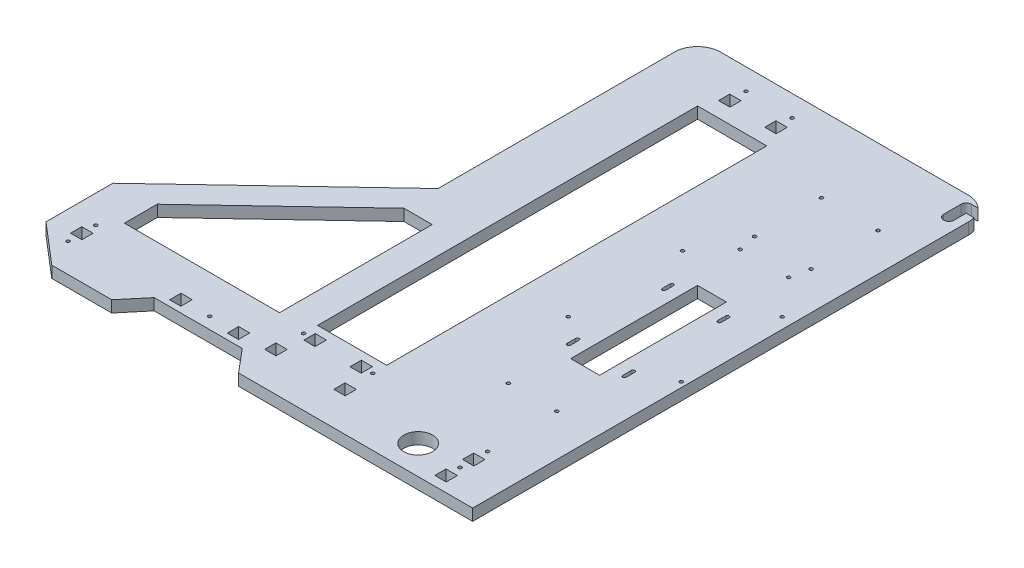
SolidWorks part; units mm, degrees
ref_plane "Front Plane" through (0, 0, 0) normal (0, 0, 1) x (1, 0, 0)
ref_plane "Top Plane" through (0, 0, 0) normal (0, 1, 0) x (1, 0, 0)
ref_plane "Right Plane" through (0, 0, 0) normal (1, 0, 0) x (0, 0, -1)
sketch "Sketch1" plane through (0, 0, 0) normal (0, 1, 0) x (1, 0, 0)
  line L0 (0, 0) -> (-235, 0)
  line L1 (-235, 0) -> (-235, -225)
  line L2 (-235, -225) -> (-380, -362)
  line L3 (-380, -362) -> (-380, -420)
  line L4 (-380, -420) -> (-345, -450)
  line L5 (-345, -450) -> (-293, -450)
  line L6 (-293, -450) -> (-263.6315, -415)
  line L7 (-263.6315, -415) -> (-212.3685, -415)
  line L8 (-212.3685, -415) -> (-183, -450)
  line L9 (-183, -450) -> (0, -450)
  line L10 (0, 0) -> (0, -450)
  line L12 (-293, -450) -> (-183, -450) construction
  dimension "D3" = 235
  dimension "D5" = 58
  dimension "D13" = 190
  dimension "D7" = 35
  dimension "D15" = 52
  dimension "D12" = 30
  dimension "D10" = 35
  dimension "D6" = 380
  dimension "D4" = 450
  dimension "D2" = 50
  dimension "D8" = 50
  dimension "D9" = 110
extrude "Boss-Extrude1" add sketch "Sketch1" along normal blind 10
sketch "Sketch16" plane through (0, 10, 0) normal (0, 1, 0) x (1, 0, 0)
  line L0 (0, -450) -> (20, -450)
  line L1 (20, -450) -> (20, 0)
  line L2 (20, 0) -> (0, 0)
  line L3 (0, 0) -> (0, -450)
  dimension "D1" = 20
  dimension "D2" = 90
extrude "Boss-Extrude2" add sketch "Sketch16" against normal through all
sketch "Sketch2" plane through (0, 10, 0) normal (0, 1, 0) x (1, 0, 0)
  line L0 (-235, -225) -> (-235, -415) construction
  line L1 (-263.6315, -415) -> (-212.3685, -415) construction
  line L2 (-345, -450) -> (-345, -328.931) construction
  line L3 (-235, -225) -> (-380, -362) construction
  line L4 (-345, -358.5097) -> (-235, -254.5787)
  line L5 (-235, -254.5787) -> (-210.5, -254.5787)
  line L6 (-210.5, -254.5787) -> (-210.5, -387)
  line L7 (-210.5, -387) -> (-345, -387)
  line L8 (-345, -387) -> (-345, -358.5097)
  line L9 (0, -450) -> (0, 0) construction
  line L10 (-184.5, -380) -> (-124.5, -380)
  line L11 (-184.5, -380) -> (-184.5, -50.425)
  line L12 (-184.5, -50.425) -> (-124.5, -50.425)
  line L13 (-124.5, -380) -> (-124.5, -50.425)
  line L14 (-124.5, -392.1) -> (-184.5, -392.1) construction
  line L15 (-16, -450) -> (-16, 0) construction
  line L16 (20, 0) -> (-235, 0) construction
  line L17 (-355.9, -440.6571) -> (-355.9, -339.2297) construction
  line L18 (-20.925, -441.85) -> (-11.075, -441.85)
  line L19 (-20.925, -441.85) -> (-20.925, -432.15)
  line L20 (-20.925, -432.15) -> (-11.075, -432.15)
  line L21 (-11.075, -441.85) -> (-11.075, -432.15)
  line L22 (-20.925, -441.85) -> (-11.075, -432.15) construction
  line L23 (-20.925, -432.15) -> (-11.075, -441.85) construction
  line L24 (-20.925, -417.85) -> (-11.075, -417.85)
  line L25 (-20.925, -417.85) -> (-20.925, -408.15)
  line L26 (-20.925, -408.15) -> (-11.075, -408.15)
  line L27 (-11.075, -417.85) -> (-11.075, -408.15)
  line L28 (-20.925, -417.85) -> (-11.075, -408.15) construction
  line L29 (-20.925, -408.15) -> (-11.075, -417.85) construction
  line L30 (-380, -420) -> (-345, -450) construction
  line L32 (-350.975, -408.15) -> (-360.825, -408.15)
  line L33 (-350.975, -408.15) -> (-350.975, -417.85)
  line L34 (-350.975, -417.85) -> (-360.825, -417.85)
  line L35 (-360.825, -408.15) -> (-360.825, -417.85)
  line L36 (-350.975, -408.15) -> (-360.825, -417.85) construction
  line L37 (-350.975, -417.85) -> (-360.825, -408.15) construction
  line L38 (-183, -450) -> (20, -450) construction
  line L39 (-183, -450) -> (20, -450) construction
  line L40 (-173.749, -32.425) -> (-113.749, -32.425) construction
  line L41 (-154.5, -50.425) -> (-154.5, -32.425) construction
  line L42 (-179.425, -27.575) -> (-169.575, -27.575)
  line L43 (-179.425, -27.575) -> (-179.425, -37.275)
  line L44 (-179.425, -37.275) -> (-169.575, -37.275)
  line L45 (-169.575, -27.575) -> (-169.575, -37.275)
  line L46 (-179.425, -27.575) -> (-169.575, -37.275) construction
  line L47 (-179.425, -37.275) -> (-169.575, -27.575) construction
  line L48 (-129.575, -37.275) -> (-139.425, -27.575) construction
  line L49 (-129.575, -27.575) -> (-139.425, -37.275) construction
  line L50 (-139.425, -27.575) -> (-139.425, -37.275)
  line L51 (-129.575, -37.275) -> (-139.425, -37.275)
  line L52 (-129.575, -27.575) -> (-129.575, -37.275)
  line L53 (-129.575, -27.575) -> (-139.425, -27.575)
  line L54 (-174.5, -32.425) -> (-174.5, -18.425) construction
  line L55 (-134.5, -32.425) -> (-134.5, -18.425) construction
  line L56 (-154.5, -380) -> (-154.5, -450) construction
  line L57 (-174.5, -392.1) -> (-134.5, -392.1) construction
  line L58 (-129.65, -397.025) -> (-139.35, -387.175) construction
  line L59 (-179.35, -387.175) -> (-169.65, -387.175)
  line L60 (-179.35, -387.175) -> (-179.35, -397.025)
  line L61 (-179.35, -397.025) -> (-169.65, -397.025)
  line L62 (-169.65, -387.175) -> (-169.65, -397.025)
  line L63 (-179.35, -387.175) -> (-169.65, -397.025) construction
  line L64 (-179.35, -397.025) -> (-169.65, -387.175) construction
  line L65 (-129.65, -387.175) -> (-139.35, -397.025) construction
  line L66 (-139.35, -387.175) -> (-139.35, -397.025)
  line L67 (-129.65, -397.025) -> (-139.35, -397.025)
  line L68 (-129.65, -387.175) -> (-129.65, -397.025)
  line L69 (-129.65, -387.175) -> (-139.35, -387.175)
  line L70 (-119.575, -420.95) -> (-129.425, -411.25) construction
  line L71 (-189.425, -411.25) -> (-179.575, -411.25)
  line L72 (-189.425, -411.25) -> (-189.425, -420.95)
  line L73 (-189.425, -420.95) -> (-179.575, -420.95)
  line L74 (-179.575, -411.25) -> (-179.575, -420.95)
  line L75 (-189.425, -411.25) -> (-179.575, -420.95) construction
  line L76 (-189.425, -420.95) -> (-179.575, -411.25) construction
  line L77 (-119.575, -411.25) -> (-129.425, -420.95) construction
  line L78 (-129.425, -411.25) -> (-129.425, -420.95)
  line L79 (-119.575, -420.95) -> (-129.425, -420.95)
  line L80 (-119.575, -411.25) -> (-119.575, -420.95)
  line L81 (-119.575, -411.25) -> (-129.425, -411.25)
  line L82 (-360.825, -408.15) -> (-11.075, -408.15) construction
  circle A0 centre (-16, -425) radius 1.45
  circle A1 centre (-16, -401) radius 1.45
  circle A2 centre (-355.9, -425) radius 1.45
  circle A3 centre (-355.9, -401) radius 1.45
  circle A4 centre (-174.5, -18.425) radius 1.45
  circle A5 centre (-134.5, -18.425) radius 1.45
  circle A6 centre (-124.5, -392.1) radius 1.45
  circle A7 centre (-184.5, -392.1) radius 1.45
  point P25 (-16, -437)
  point P30 (-16, -413)
  point P44 (-355.9, -413)
  point P61 (-174.5, -32.425)
  point P72 (-134.5, -32.425)
  point P85 (-174.5, -392.1)
  point P94 (-134.5, -392.1)
  point P95 (-184.5, -416.1)
  point P104 (-124.5, -416.1)
  point P105 (-154.5, -392.1)
  dimension "D13" = 2.9
  dimension "D14" = 2.9
  dimension "D23" = 2.9
  dimension "D24" = 2.9
  dimension "D31" = 2.9
  dimension "D37" = 2.9
  dimension "D1" = 21.5
  dimension "D2" = 28
  dimension "D3" = 24.5
  dimension "D4" = 60
  dimension "D7" = 26
  dimension "D8" = 9.7
  dimension "D9" = 9.85
  dimension "D10" = 9.85
  dimension "D11" = 9.7
  dimension "D12" = 24
  dimension "D15" = 24
  dimension "D19" = 9.85
  dimension "D20" = 9.7
  dimension "D26" = 12
  dimension "D27" = 9.85
  dimension "D28" = 9.7
  dimension "D33" = 9.7
  dimension "D38" = 9.85
  dimension "D39" = 9.7
  dimension "D41" = 24
  dimension "D34" = 30
  dimension "D36" = 12.1
  dimension "D30" = 18
  dimension "D29" = 40
  dimension "D17" = 13
  dimension "D32" = 14
  dimension "D35" = 20
  dimension "D16" = 12
  dimension "D21" = 90
  dimension "D25" = 24
  dimension "D5" = 359.75
  dimension "D22" = 349.75
  dimension "D40" = 30
  dimension "D6" = 70
  dimension "D42" = 0
  dimension "D43" = 0
  dimension "D18" = 16
  dimension "D44" = 9.85
extrude "Cut-Extrude1" cut sketch "Sketch2" against normal through all
fillet "Fillet1" radius 20 2 edges at (-235, 5, 0) (20, 5, 0)
sketch "Sketch11" plane through (0, 10, 0) normal (0, 1, 0) x (1, 0, 0)
  line L0 (-124.5, -215.2125) -> (20, -215.2125) construction
  line L1 (20, -450) -> (20, -20) construction
  line L3 (-52.25, -215.2125) -> (-52.25, -450) construction
  line L6 (-124.5, -380) -> (-124.5, -50.425) construction
  line L8 (-183, -450) -> (20, -450) construction
  circle A0 centre (-52.25, -425) radius 12.5
  circle A1 centre (-16, -425) radius 1.45 construction
  dimension "D1" = 25
  dimension "D2" = 0
  dimension "D3" = 0
extrude "WiringHole" cut sketch "Sketch11" against normal through all
sketch "Sketch9" [suppressed] plane through (0, 10, 0) normal (0, 1, 0) x (1, 0, 0)
  line L0 (-52.25, -412.5) -> (-52.25, 0) construction
  line L1 (0, 0) -> (-215, 0) construction
  line L2 (-124.5, -215.2125) -> (20, -215.2125) construction
  line L3 (-124.5, -380) -> (-124.5, -50.425) construction
  line L4 (-4.75, -126.7125) -> (-4.75, -303.7125) construction
  line L6 (-99.75, -126.7125) -> (-4.75, -126.7125) construction
  line L7 (-4.75, -303.7125) -> (-99.75, -303.7125) construction
  line L8 (-99.75, -303.7125) -> (-99.75, -126.7125) construction
  line L9 (20, -450) -> (20, -20) construction
  circle A0 centre (-52.25, -425) radius 12.5 construction
  circle A1 centre (-99.75, -126.7125) radius 1.45
  circle A2 centre (-4.75, -126.7125) radius 1.45
  circle A3 centre (-4.75, -303.7125) radius 1.45
  circle A4 centre (-99.75, -303.7125) radius 1.45
  dimension "D3" = 2.9
  dimension "D4" = 2.9
  dimension "D1" = 95
  dimension "D2" = 177
  dimension "D5" = 47.5
extrude "MountingHoles-PSU" [suppressed] cut sketch "Sketch9" against normal through all
sketch "Sketch10" plane through (0, 10, 0) normal (0, 1, 0) x (1, 0, 0)
  line L0 (-124.5, -215.2125) -> (20, -215.2125) construction
  line L1 (20, -450) -> (20, -20) construction
  line L2 (-49.75, -240.2125) -> (-24.75, -240.2125) construction
  line L3 (-37.25, -210.225) -> (-37.25, 0) construction
  line L4 (-52.25, -215.2125) -> (-52.25, -184.5972) construction
  line L7 (-124.5, -380) -> (-124.5, -50.425) construction
  line L8 (-49.75, -295.2125) -> (-24.75, -295.2125)
  line L9 (-49.75, -295.2125) -> (-49.75, -185.2125)
  line L10 (-49.75, -185.2125) -> (-24.75, -185.2125)
  line L11 (-24.75, -295.2125) -> (-24.75, -185.2125)
  line L12 (-49.75, -295.2125) -> (-24.75, -185.2125) construction
  line L13 (-49.75, -185.2125) -> (-24.75, -295.2125) construction
  line L15 (0, 0) -> (-215, 0) construction
  line L17 (-37.25, -210.225) -> (-37.25, -450) construction
  line L18 (-183, -450) -> (20, -450) construction
  line L19 (-64.75, -215.2125) -> (-39.75, -215.2125) construction
  line L20 (-37.25, -295.2125) -> (-37.25, -185.2125) construction
  dimension "D1" = 25
  dimension "D2" = 110
  dimension "D3" = 0
  dimension "D4" = 0
  dimension "D5" = 0
  dimension "D6" = 25
  dimension "D7" = 15
extrude "WiringSlot" cut sketch "Sketch10" against normal through all
sketch "CenterLines" plane through (0, 10, 0) normal (0, 1, 0) x (1, 0, 0)
  line L0 (-37.25, -295.2125) -> (-37.25, -185.2125) construction
  line L1 (-49.75, -295.2125) -> (-24.75, -295.2125) construction
  line L2 (-24.75, -185.2125) -> (-49.75, -185.2125) construction
  line L3 (-49.75, -240.2125) -> (-24.75, -240.2125) construction
  line L4 (-49.75, -185.2125) -> (-49.75, -295.2125) construction
  line L5 (-24.75, -295.2125) -> (-24.75, -185.2125) construction
ref_plane "Plane1" through (-37.25, 0, 0) normal (1, 0, 0) x (0, 0, -1)
sketch "Sketch6" plane through (0, 10, 0) normal (0, 1, 0) x (1, 0, 0)
  line L0 (-37.25, -295.2125) -> (-37.25, -185.2125) construction
  line L1 (-61.35, -240.2125) -> (-13.15, -240.2125) construction
  line L2 (-13.15, -195.7625) -> (-13.15, -278.2625) construction
  line L3 (-49.75, -295.2125) -> (-24.75, -295.2125) construction
  line L4 (-49.75, -240.2125) -> (-24.75, -240.2125) construction
  line L5 (-24.75, -185.2125) -> (-49.75, -185.2125) construction
  line L6 (-13.15, -195.7625) -> (-13.15, -202.7625) construction
  line L7 (-11.7, -195.7625) -> (-11.7, -202.7625)
  line L8 (-14.6, -195.7625) -> (-14.6, -202.7625)
  line L9 (-49.75, -240.2125) -> (-24.75, -240.2125) construction
  line L10 (-49.75, -185.2125) -> (-49.75, -295.2125) construction
  line L11 (-24.75, -295.2125) -> (-24.75, -185.2125) construction
  line L12 (-13.15, -285.2625) -> (-13.15, -278.2625) construction
  line L13 (-14.6, -285.2625) -> (-14.6, -278.2625)
  line L14 (-61.35, -277.6625) -> (-61.35, -202.7625) construction
  line L15 (-13.15, -285.2625) -> (-13.15, -202.7625) construction
  line L16 (-11.7, -285.2625) -> (-11.7, -278.2625)
  arc A2 (-11.7, -195.7625) -> (-14.6, -195.7625) centre (-13.15, -195.7625) ccw
  arc A3 (-14.6, -202.7625) -> (-11.7, -202.7625) centre (-13.15, -202.7625) ccw
  circle A4 centre (-61.35, -277.6625) radius 1.45
  circle A6 centre (-61.35, -202.7625) radius 1.45
  arc A8 (-14.6, -285.2625) -> (-11.7, -285.2625) centre (-13.15, -285.2625) ccw
  arc A9 (-11.7, -278.2625) -> (-14.6, -278.2625) centre (-13.15, -278.2625) ccw
  point P20 (-13.15, -199.2625)
  point P25 (-13.15, -281.7625)
  dimension "D6" = 0
  dimension "D8" = 2.9
  dimension "D12" = 2.9
  dimension "D4" = 1.45
  dimension "D5" = 1.45
  dimension "D11" = 82.5
  dimension "D14" = 74.9
  dimension "D2" = 24.1
  dimension "D3" = 48.2
  dimension "D9" = 7
  dimension "D10" = 7
extrude "MountingHoles-RAMPS" cut sketch "Sketch6" against normal through all
mirror "Mirror1" about plane through (-37.25, 0, 0) normal (1, 0, 0) of "MountingHoles-RAMPS"
sketch "Sketch5" plane through (0, 10, 0) normal (0, 1, 0) x (1, 0, 0)
  line L0 (-24.75, -240.2125) -> (-49.75, -240.2125) construction
  line L3 (-24.75, -295.2125) -> (-24.75, -185.2125) construction
  line L5 (-49.75, -185.2125) -> (-49.75, -295.2125) construction
  line L7 (-16.25, -139.7125) -> (-58.25, -139.7125) construction
  line L8 (-16.25, -340.7125) -> (-58.25, -340.7125) construction
  line L9 (-37.25, -240.2125) -> (-37.25, -139.7125) construction
  line L10 (-37.25, -240.2125) -> (-37.25, -340.7125) construction
  circle A0 centre (-58.25, -139.7125) radius 1.45
  circle A1 centre (-16.25, -139.7125) radius 1.45
  circle A2 centre (-16.25, -340.7125) radius 1.45
  circle A3 centre (-58.25, -340.7125) radius 1.45
  point P17 (-37.25, -139.7125)
  point P22 (-37.25, -340.7125)
  dimension "D2" = 2.9
  dimension "D5" = 2.9
  dimension "D6" = 2.9
  dimension "D7" = 2.9
  dimension "D3" = 201
  dimension "D4" = 100.5
  dimension "D8" = 21
  dimension "D9" = 21
  dimension "D10" = 100.5
extrude "MountingHoles-Melzi" cut sketch "Sketch5" against normal through all
sketch "Sketch13" plane through (0, 0, 0) normal (0, -1, 0) x (-1, 0, 0)
  line L0 (49.75, -215.2125) -> (124.5, -215.2125) construction
  line L1 (124.5, -380) -> (124.5, -50.425) construction
  line L2 (82.25, -264.7275) -> (82.25, -165.6975) construction
  line L3 (37.25, -295.2125) -> (37.25, -185.2125) construction
  line L4 (49.75, -185.2125) -> (49.75, -295.2125) construction
  line L6 (82.25, -264.7275) -> (-15.65, -264.7275) construction
  circle A0 centre (82.25, -165.6975) radius 1.45
  circle A1 centre (82.25, -264.7275) radius 1.45
  circle A2 centre (-10.59, -172.1775) radius 1.45
  circle A3 centre (-15.65, -264.7275) radius 1.45
  point P11 (82.25, -215.2125)
  dimension "D8" = 2.9
  dimension "D6" = 2.9
  dimension "D1" = 2.9
  dimension "D2" = 49.515
  dimension "D3" = 45
  dimension "D4" = 6.48
  dimension "D5" = 92.84
  dimension "D7" = 97.9
extrude "Mountingholes-Smoothieboard" cut sketch "Sketch13" against normal through all
mirror "Flipped" [suppressed] about plane through (-37.25, 0, 0) normal (1, 0, 0)
sketch "Sketch21" plane through (0, 10, 0) normal (0, 1, 0) x (1, 0, 0)
  line L0 (-37.25, -185.2125) -> (-37.25, 0) construction
  line L1 (-24.75, -185.2125) -> (-49.75, -185.2125) construction
  line L2 (0, 0) -> (-215, 0) construction
  line L3 (-37.25, -94.7125) -> (-23.3697, -94.7125) construction
  circle A0 centre (-12.75, -65.7125) radius 1.45
  circle A1 centre (-61.75, -65.7125) radius 1.45
  circle A2 centre (-61.75, -123.7125) radius 1.45
  circle A3 centre (-12.75, -123.7125) radius 1.45
  circle A4 centre (-16.25, -139.7125) radius 1.45 construction
  dimension "D1" = 2.9
  dimension "D2" = 24.5
  dimension "D3" = 29
  dimension "D4" = 45
extrude "Pi" cut sketch "Sketch21" against normal through all
sketch "Sketch17" plane through (0, 10, 0) normal (0, 1, 0) x (1, 0, 0)
  line L0 (0, 0) -> (20, 0) construction
  line L1 (20, -23.6361) -> (20, 0) construction
  line L2 (20, -450) -> (20, -20) construction
  line L3 (20, -10) -> (8, -10) construction
  line L4 (20, -14.5) -> (8, -14.5)
  line L5 (20, -5.5) -> (8, -5.5)
  arc A0 (20, -14.5) -> (20, -5.5) centre (20, -10) ccw
  arc A1 (8, -5.5) -> (8, -14.5) centre (8, -10) ccw
  point P8 (14, -10)
  dimension "D1" = 9
  dimension "D2" = 12
  dimension "D3" = 10
extrude "Cut-Extrude3" cut sketch "Sketch17" against normal through all
sketch "Sketch18" plane through (0, 10, 0) normal (0, 1, 0) x (1, 0, 0)
  line L0 (8, -5.5) -> (8, -14.5) construction
  line L1 (3.5, -10) -> (8, -10) construction
  line L2 (8, -10) -> (8, -25) construction
  line L3 (12.5, -10) -> (12.5, -25)
  line L4 (3.5, -10) -> (3.5, -25)
  arc A0 (8, -5.5) -> (8, -14.5) centre (8, -10) ccw construction
  arc A1 (12.5, -10) -> (3.5, -10) centre (8, -10) ccw
  arc A2 (3.5, -25) -> (12.5, -25) centre (8, -25) ccw
  point P10 (8, -17.5)
  dimension "D1" = 9
  dimension "D2" = 0
  dimension "D3" = 15
extrude "Cut-Extrude4" cut sketch "Sketch18" against normal through all
sketch "Sketch19" plane through (0, 10, 0) normal (0, 1, 0) x (1, 0, 0)
  line L0 (-2, -25) -> (18, -25) construction
  line L1 (8, -25) -> (8, -5.5) construction
  circle A0 centre (18, -25) radius 1.45
  arc A1 (8, -5.5) -> (3.5, -10) centre (8, -10) ccw construction
  circle A2 centre (-2, -25) radius 1.45
  dimension "D2" = 2.9
extrude "Cut-Extrude5" [suppressed] cut sketch "Sketch19" against normal through all
sketch "Sketch22" plane through (0, 10, 0) normal (0, 1, 0) x (1, 0, 0)
  line L0 (-276.218, -430) -> (-199.782, -430)
  line L1 (-293, -450) -> (-263.6315, -415) construction
  line L2 (-212.3685, -415) -> (-183, -450) construction
  line L3 (-199.782, -430) -> (-212.3685, -415)
  line L4 (-212.3685, -415) -> (-263.6315, -415)
  line L5 (-263.6315, -415) -> (-276.218, -430)
  dimension "D1" = 15
extrude "Boss-Extrude3" add sketch "Sketch22" against normal through all
sketch "Sketch23" plane through (0, 10, 0) normal (0, 1, 0) x (1, 0, 0)
  line L0 (-238, -430) -> (-238, -387) construction
  line L1 (-276.218, -430) -> (-199.782, -430) construction
  line L2 (-345, -387) -> (-210.5, -387) construction
  line L3 (-213, -420) -> (-263, -420) construction
  line L4 (-179.35, -387.175) -> (-179.35, -397.025) construction
  line L5 (-267.85, -415.075) -> (-258.15, -415.075)
  line L6 (-267.85, -415.075) -> (-267.85, -424.925)
  line L7 (-267.85, -424.925) -> (-258.15, -424.925)
  line L8 (-258.15, -415.075) -> (-258.15, -424.925)
  line L9 (-267.85, -415.075) -> (-258.15, -424.925) construction
  line L10 (-267.85, -424.925) -> (-258.15, -415.075) construction
  line L11 (-208.15, -424.925) -> (-217.85, -415.075) construction
  line L12 (-208.15, -415.075) -> (-217.85, -424.925) construction
  line L13 (-217.85, -415.075) -> (-217.85, -424.925)
  line L14 (-208.15, -424.925) -> (-217.85, -424.925)
  line L15 (-208.15, -415.075) -> (-208.15, -424.925)
  line L16 (-208.15, -415.075) -> (-217.85, -415.075)
  circle A0 centre (-238, -420) radius 1.45
  point P19 (-238, -420)
  dimension "D4" = 2.9
  dimension "D1" = 9.7
  dimension "D3" = 10
extrude "Cut-Extrude6" cut sketch "Sketch23" against normal through all
equation "\"Y-ROD-SPACING\"=75"
equation "\"Y-BED-OFFSET\"=2"
equation "\"Y-BED-ROD-INSET\"=3.5"
equation "\"T-SLOT-NUT-FILLET-RADIUS\"=0.5"
equation "\"T-SLOT-SCREW-SHAFT-RADIUS\"=1.55"
equation "\"T-SLOT-SCREW-SHAFT-CUTOUT-LENGTH\"=11"
equation "\"T-SLOT-NUT-DEPTH\"=3.5"
equation "\"T-SLOT-NUT-WIDTH\"=2.85"
equation "\"T-SLOT-NUT-END-DISTANCE\"=8"
equation "\"ACRYLIC-TAB-CUTOUT-SIZE\"=\"ACRYLIC-THICKNESS\"+\"ACRYLIC-TAB-TOLERANCE\"*2"
equation "\"ACRYLIC-TAB-WIDTH\"=\"ACRYLIC-THICKNESS\""
equation "\"ACRYLIC-M3-HOLE\"=2.9"
equation "\"SMOOTHROD-CAP-SCREW-DISTANCE\"=20"
equation "\"FRAME-WIDTH-INNER\"=370"
equation "\"D24@Sketch2\"=\"ACRYLIC-M3-HOLE\""
equation "\"D23@Sketch2\"=\"ACRYLIC-M3-HOLE\""
equation "\"D19@Sketch2\"=\"ACRYLIC-THICKNESS\"-\"KERF\"*2"
equation "\"D20@Sketch2\"=\"ACRYLIC-TAB-WIDTH\"-\"KERF\"*4"
equation "\"D37@Sketch2\"=\"ACRYLIC-M3-HOLE\""
equation "\"D33@Sketch2\"=\"ACRYLIC-TAB-WIDTH\"-\"KERF\"*4"
equation "\"D38@Sketch2\"=\"ACRYLIC-THICKNESS\"-\"KERF\"*2"
equation "\"D39@Sketch2\"=\"ACRYLIC-TAB-WIDTH\"-\"KERF\"*4"
equation "\"D13@Sketch2\"=\"ACRYLIC-M3-HOLE\""
equation "\"D14@Sketch2\"=\"ACRYLIC-M3-HOLE\""
equation "\"D8@Sketch2\"=\"ACRYLIC-TAB-WIDTH\"-\"KERF\"*4"
equation "\"D9@Sketch2\"=\"ACRYLIC-THICKNESS\"-\"KERF\"*2"
equation "\"D10@Sketch2\"=\"ACRYLIC-THICKNESS\"-\"KERF\"*2"
equation "\"D11@Sketch2\"=\"ACRYLIC-TAB-WIDTH\"-\"KERF\"*4"
equation "\"D31@Sketch2\"=\"ACRYLIC-M3-HOLE\""
equation "\"D27@Sketch2\"=\"ACRYLIC-THICKNESS\"-\"KERF\"*2"
equation "\"D28@Sketch2\"=\"ACRYLIC-TAB-WIDTH\"-\"KERF\"*4"
equation "\"NEMA17-HOLE-SPACING\"=31"
equation "\"NEMA17-CENTRAL-CUTOUT\"=22.5"
equation "\"Z-BRACKET-REACH\"=57"
equation "\"TOP-BRACKET-SPACING\"=40"
equation "\"D29@Sketch2\"=\"TOP-BRACKET-SPACING\""
equation "\"ACRYLIC-THICKNESS\"=10"
equation "\"SMOOTHROD-Z-LENGTH\"=350"
equation "\"D5@Sketch2\"=\"SMOOTHROD-Z-LENGTH\"-\"SMOOTHROD-TIGHTENING-HEADROOM\"+10"
equation "\"SMOOTHROD-X-LENGTH\"=350"
equation "\"SMOOTHROD-Y-LENGTH\"=350"
equation "\"D22@Sketch2\"=\"SMOOTHROD-Y-LENGTH\"-\"SMOOTHROD-TIGHTENING-HEADROOM\""
equation "\"SMOOTHROD-TIGHTENING-HEADROOM\"=.25"
equation "\"X-ROD-SPACING\"=45"
equation "\"Z-ROD-SPACING\"=17.5"
equation "\"LEADSCREW-Z-LENGTH\"=300"
equation "\"SCREW-HEAD-RADIUS\"=6"
equation "\"PRINTED-X-SMOOTHROD-DIAMETER\"=8.8"
equation "\"PRINTED-X-SMOOTHROD-CUTOUT\"=10"
equation "\"PRINTED-X-BASE-HEIGHT\"=10"
equation "\"PRINTED-LM8UU-CUTOUT-SIZE\"=15.5"
equation "\"PRINTED-LM8UU-CUTOUT-LENGTH\"=24.5"
equation "\"PRINTED-X-IDLER-HEIGHT\"=16"
equation "\"PSU-MOUNTING-WIDTH\"=95"
equation "\"PSU-MOUNTING-HEIGHT\"=177"
equation "\"D1@Sketch9\"=\"PSU-MOUNTING-WIDTH\""
equation "\"D3@Sketch9\"=\"ACRYLIC-M3-HOLE\""
equation "\"D1@Boss-Extrude1\"=\"ACRYLIC-THICKNESS\""
equation "\"D6@Sketch1\"=\"SMOOTHROD-Y-LENGTH\"+30"
equation "\"D4@Sketch9\"=\"ACRYLIC-M3-HOLE\""
equation "\"D2@Sketch9\"=\"PSU-MOUNTING-HEIGHT\""
equation "\"D5@Sketch9\"=\"PSU-MOUNTING-WIDTH\"/2"
equation "\"D4@Sketch1\"=\"SMOOTHROD-Z-LENGTH\"+100"
equation "\"D8@Sketch6\"=\"ACRYLIC-M3-HOLE\""
equation "\"D12@Sketch6\"=\"ACRYLIC-M3-HOLE\""
equation "\"D2@Sketch5\"=\"ACRYLIC-M3-HOLE\""
equation "\"D5@Sketch5\"=\"ACRYLIC-M3-HOLE\""
equation "\"D6@Sketch5\"=\"ACRYLIC-M3-HOLE\""
equation "\"D7@Sketch5\"=\"ACRYLIC-M3-HOLE\""
equation "\"D1@Sketch13\"=\"ACRYLIC-M3-HOLE\""
equation "\"D6@Sketch13\"=\"ACRYLIC-M3-HOLE\""
equation "\"D8@Sketch13\"=\"ACRYLIC-M3-HOLE\""
equation "\"D4@Sketch6\"=\"ACRYLIC-M3-HOLE\"/2"
equation "\"D5@Sketch6\"=\"ACRYLIC-M3-HOLE\"/2"
equation "\"Y-BED-SCREW-SPACING\"=209"
equation "\"Y-BED-SCREW-CUTOUT-SLOT-HEIGHT\"=2.5"
equation "\"ACRYLIC-THICKNESS2\"=4.5"
equation "\"ACRYLIC-TAB-TOLERANCE\"=-.05"
equation "\"Z-ROD-INSET\"=13.5"
equation "\"SCREW-LENGTH-FRAME\"=\"ACRYLIC-THICKNESS\" + 10"
equation "\"SCREW-LENGTH-MOTOR\"=\"ACRYLIC-THICKNESS\" + 5"
equation "\"SCREW-LENGTH-EXTRUDER\"=28"
equation "\"Y-BELT-TO-ROD-DISTANCE\"=20"
equation "\"SPOOL-HOLDER-ROD-SPACING\"=150"
equation "\"ACRYLIC-X-CARRIAGE-WIDTH\"=55"
equation "\"ACRYLIC-X-CARRIAGE-HEIGHT\"=75"
equation "\"ACRYLIC-X-CARRIAGE-LM8UU-CUTOUT-WIDTH\"=24.25"
equation "\"ACRYLIC-X-CARRIAGE-SCREW-SPACING-X\"=15"
equation "\"ACRYLIC-X-CARRIAGE-SCREW-SPACING-Y\"=33"
equation "\"ACRYLIC-X-CARRIAGE-CENTER-TAB-SPACING\"=14"
equation "\"ACRYLIC-X-CARRIAGE-EXTRUDER-OFFSET\"=26"
equation "\"ACRYLIC-X-CARRIAGE-EXTRUDER-ANGLE\"=90"
equation "\"ACRYLIC-X-CARRIAGE-EXTRUDER-SHELF-DEPTH\"=\"ACRYLIC-X-CARRIAGE-EXTRUDER-OFFSET\" + 28"
equation "\"ACRYLIC-X-CARRIAGE-EXTRUDER-BRACE-SPACING\"=23"
equation "\"ACRYLIC-X-CARRIAGE-EXTRUDER-BRACE-TAB-OFFSET\"=20"
equation "\"ACRYLIC-X-CARRIAGE-EXTRUDER-BRACE-HEIGHT\"=35"
equation "\"ACRYLIC-X-CARRIAGE-EXTRUDER-BRACE-SCREW-SPACING\"=22"
equation "\"D1@Sketch19\"=\"SMOOTHROD-CAP-SCREW-DISTANCE\"/2"
equation "\"D2@Sketch19\"=\"ACRYLIC-M3-HOLE\""
equation "\"D1@Sketch21\"=\"ACRYLIC-M3-HOLE\""
equation "\"KERF\"=0.075"
equation "\"PRINTED-M3-HOLE\"=3.5"
equation "\"PRINTED-M3-NUT-AF\"=6.25"
equation "\"ACRYLIC-X-CARRIAGE-LM8UU-CUTOUT-HEIGHT\"=11.0"
equation "\"ACRYLIC-X-CARRIAGE-DUAL-WIDTH-MULTIPLIER\"=1.65"
equation "\"ACRYLIC-X-CARRIAGE-DUAL-HOTEND-SPACING\"=42"
equation "\"ACRYLIC-X-CARRIAGE-DUAL-WIDTH\"=75"
equation "\"ACRYLIC-X-CARRIAGE-DUAL-FAN-OFFSET\"=52"
equation "\"ACRYLIC-X-CARRIAGE-DUAL-FAN-HEIGHT\"=20"
equation "\"ACRYLIC-X-CARRIAGE-DUAL-HOTEND-SEPARATION\"=36"
equation "\"ACRYLIC-X-CARRIAGE-DUAL-MOUNT-PLATE-DEPTH\"=75"
equation "\"ACRYLIC-X-CARRIAGE-DUAL-MOUNT-BRACE-WIDTH\"=33"
equation "\"ACRYLIC-X-CARRIAGE-DUAL-MOUNT-SCREW-WIDTH\"=40"
equation "\"BLOWER-FAN-WIDTH\"=15"
equation "\"D44@Sketch2\"=\"ACRYLIC-THICKNESS\"-\"KERF\"*2"
equation "\"D1@Sketch23\"=10-\"KERF\"*4"
equation "\"D4@Sketch23\"=\"ACRYLIC-M3-HOLE\""
